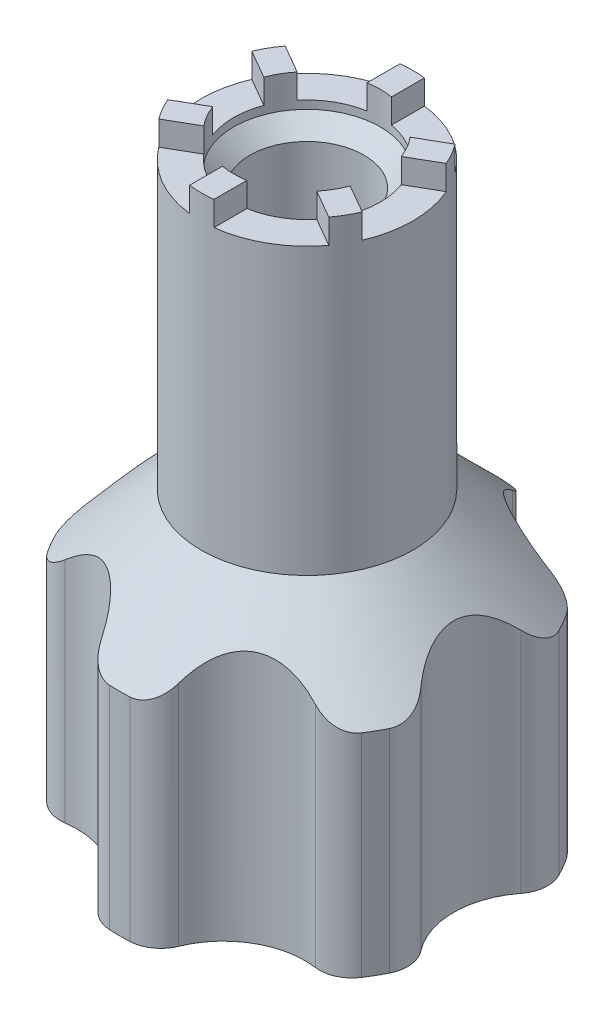
SolidWorks part; units mm, degrees
ref_plane "Спереди" through (0, 0, 0) normal (0, 0, 1) x (1, 0, 0)
ref_plane "Сверху" through (0, 0, 0) normal (0, 1, 0) x (1, 0, 0)
ref_plane "Справа" through (0, 0, 0) normal (1, 0, 0) x (0, 0, -1)
sketch "Эскиз1" plane through (0, 0, 0) normal (0, 0, 1) x (1, 0, 0)
  line L0 (0, 0) -> (0, -8.3854) construction
  line L1 (0, 0) -> (-6.75, 0) construction
  line L2 (-6.75, 0) -> (-11.5, 0)
  line L3 (-11.5, 0) -> (-11.5, 13)
  line L4 (-11.5, 13) -> (-6.5, 18)
  line L5 (-6.5, 18) -> (-6.5, 37)
  line L6 (-6.5, 37) -> (-4.5, 37)
  line L7 (-3.5, 34) -> (-3.5, 18.5)
  line L8 (-3.5, 18.5) -> (0, 18.5)
  line L9 (0, 18.5) -> (0, 14.5)
  line L10 (0, 14.5) -> (-5, 14.5)
  line L11 (-5, 14.5) -> (-5, 13.5)
  line L12 (-5, 13.5) -> (-6.75, 13.5)
  line L13 (-6.75, 13.5) -> (-6.75, 0)
  line L14 (-4.5, 37) -> (-4.5, 35)
  line L15 (-4.5, 35) -> (-3.5, 34)
  dimension "D1" = 23
  dimension "D2" = 13
  dimension "D3" = 37
  dimension "D4" = 19
  dimension "D5" = 13
  dimension "D6" = 13.5
  dimension "D7" = 10
  dimension "D8" = 1
  dimension "D9" = 13.5
  dimension "D10" = 7
  dimension "D11" = 9
  dimension "D12" = 2
  dimension "D13" = 45
revolve "Повернуть1" add sketch "Эскиз1" angle 360 about L0
sketch "Эскиз2" plane through (0, 37, 0) normal (0, 1, 0) x (1, 0, 0)
  line L0 (0, 0) -> (0, 5.362) construction
  line L1 (-0.75, 6.4566) -> (-0.75, 3.4187)
  line L2 (0.75, 6.4566) -> (0.75, 3.4187)
  line L3 (5.2166, 3.8778) -> (2.5857, 2.3589)
  line L4 (5.9666, 2.5788) -> (3.3357, 1.0598)
  line L5 (5.9666, -2.5788) -> (3.3357, -1.0598)
  line L6 (5.2166, -3.8778) -> (2.5857, -2.3589)
  line L7 (0.75, -6.4566) -> (0.75, -3.4187)
  line L8 (-0.75, -6.4566) -> (-0.75, -3.4187)
  line L9 (-5.2166, -3.8778) -> (-2.5857, -2.3589)
  line L10 (-5.9666, -2.5788) -> (-3.3357, -1.0598)
  line L11 (-5.9666, 2.5788) -> (-3.3357, 1.0598)
  line L12 (-5.2166, 3.8778) -> (-2.5857, 2.3589)
  circle A0 centre (0, 0) radius 3.5
  circle A1 centre (0, 0) radius 6.5
  point P31 (0, 0)
  circle M6 centre (0, 0) radius 6.5
  dimension "D2" = 7
  dimension "D3" = 13
  dimension "D1" = 1.5
  dimension "D4" = 6
extrude "Вырез-Вытянуть1" cut sketch "Эскиз2" against normal blind 1.5 contours L12 L1 M6 | L3 L2 M6 | L5 L4 M6 | L7 L6 M6 | L9 L8 M6 | L11 L10 M6 region at (-2.5433, 37, -4.4052) region at (2.5433, 37, -4.4052) region at (-5.0866, 37, 0) region at (5.0866, 37, 0) region at (-2.5433, 37, 4.4052) region at (2.5433, 37, 4.4052)
sketch "Эскиз3" plane through (0, 0, 0) normal (0, -1, 0) x (-1, 0, 0)
  line L0 (0, 0) -> (0, -4.0376) construction
  line L1 (1.25, -9.3165) -> (2.0206, -6.4405)
  line L2 (-1.25, -9.3165) -> (-2.0206, -6.4405)
  line L3 (-7.4433, -5.7408) -> (-4.5673, -4.9702)
  line L4 (-8.6933, -3.5757) -> (-6.5879, -1.4703)
  line L5 (-8.6933, 3.5757) -> (-6.5879, 1.4703)
  line L6 (-7.4433, 5.7408) -> (-4.5673, 4.9702)
  line L7 (-1.25, 9.3165) -> (-2.0206, 6.4405)
  line L8 (1.25, 9.3165) -> (2.0206, 6.4405)
  line L9 (7.4433, 5.7408) -> (4.5673, 4.9702)
  line L10 (8.6933, 3.5757) -> (6.5879, 1.4703)
  line L11 (8.6933, -3.5757) -> (6.5879, -1.4703)
  line L12 (7.4433, -5.7408) -> (4.5673, -4.9702)
  circle A0 centre (0, 0) radius 9.4
  circle A1 centre (0, 0) radius 6.75
  point P31 (0, 0)
  circle M18 centre (0, 0) radius 6.75
  dimension "D2" = 18.8
  dimension "D4" = 13.5
  dimension "D1" = 2.5
  dimension "D3" = 15
  dimension "D5" = 6
extrude "Вырез-Вытянуть2" cut sketch "Эскиз3" against normal blind 13.5 and the other way through all contours L2 A0 L1 M18 | L4 A0 L3 M18 | L6 A0 L5 M18 | L8 A0 L7 M18 | L10 A0 L9 M18 | L12 A0 L11 M18 region at (0, 0, 7.9064) region at (-6.8472, 0, 3.9532) region at (6.8472, 0, 3.9532) region at (6.8472, 0, -3.9532) region at (-6.8472, 0, -3.9532) region at (0, 0, -7.9064)
fillet "Скругление1" radius 1 12 edges at (-8.6933, 6.75, 3.5757) (-7.4433, 6.75, 5.7408) (-8.6933, 6.75, -3.5757) (-7.4433, 6.75, -5.7408) (-1.25, 6.75, -9.3165) (1.25, 6.75, -9.3165) (8.6933, 6.75, -3.5757) (7.4433, 6.75, -5.7408) (8.6933, 6.75, 3.5757) (7.4433, 6.75, 5.7408) (1.25, 6.75, 9.3165) (-1.25, 6.75, 9.3165)
fillet "Скругление2" [suppressed] radius 3
sketch "Эскиз4" plane through (0, 0, 0) normal (0, -1, 0) x (-1, 0, 0)
  circle A0 centre (0, 0) radius 14 construction
  circle A1 centre (-14, 0) radius 5
  circle A2 centre (-7, 12.1244) radius 5
  circle A3 centre (7, 12.1244) radius 5
  circle A4 centre (14, 0) radius 5
  circle A5 centre (7, -12.1244) radius 5
  circle A6 centre (-7, -12.1244) radius 5
  point P18 (0, 0)
  dimension "D1" = 10
  dimension "D2" = 28
  dimension "D3" = 6
extrude "Вырез-Вытянуть3" cut sketch "Эскиз4" against normal through all
fillet "Скругление3" radius 2 12 edges at (8.7641, 6.5, 7.4459) (10.8304, 6.5, 3.867) (2.0663, 6.5, 11.3128) (-2.0663, 6.5, 11.3128) (-8.7641, 6.5, 7.4459) (-10.8304, 6.5, 3.867) (-10.8304, 6.5, -3.867) (-8.7641, 6.5, -7.4459) (-2.0663, 6.5, -11.3128) (2.0663, 6.5, -11.3128) (8.7641, 6.5, -7.4459) (10.8304, 6.5, -3.867)
